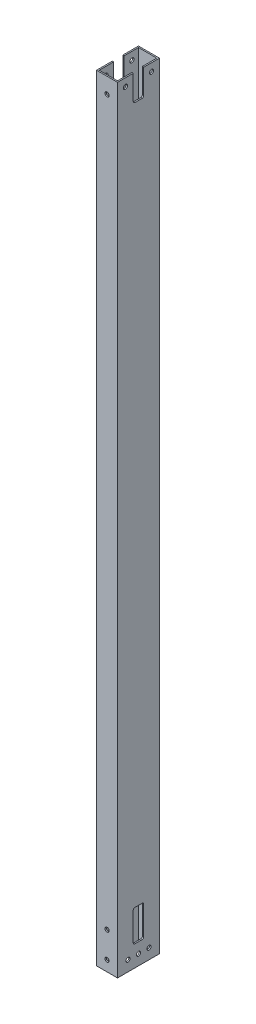
SolidWorks part; units mm, degrees
material "6061-T6 (SS)"
ref_plane "Front" through (0, 0, 0) normal (0, 0, 1) x (1, 0, 0)
ref_plane "Top" through (0, 0, 0) normal (0, 1, 0) x (1, 0, 0)
ref_plane "Right" through (0, 0, 0) normal (1, 0, 0) x (0, 0, -1)
sketch "Sketch1" plane through (0, 0, 0) normal (0, 1, 0) x (1, 0, 0)
  line L1 (12.7, 25.4) -> (-12.7, 25.4)
  line L2 (12.7, 25.4) -> (12.7, -25.4)
  line L3 (12.7, -25.4) -> (-12.7, -25.4)
  line L4 (-12.7, 25.4) -> (-12.7, -25.4)
  line L5 (12.7, 25.4) -> (-12.7, -25.4) construction
  line L6 (12.7, -25.4) -> (-12.7, 25.4) construction
  point P0 (0, 0)
  dimension "D1" = 25.4
  dimension "D2" = 50.8
extrude "Extrude-Thin1" add sketch "Sketch1" along normal blind 939.8 thin thin type one direction reverse wall 1.5875
sketch "Sketch2" plane through (-12.7, 0, 0) normal (-1, 0, 0) x (0, 0, 1)
  line L0 (-25.4, 939.8) -> (25.4, 939.8) construction
  line L1 (-6.35, 939.8) -> (6.35, 939.8)
  line L2 (-6.35, 939.8) -> (-6.35, 910.082)
  line L3 (-4.318, 908.05) -> (4.318, 908.05)
  line L4 (6.35, 939.8) -> (6.35, 910.082)
  line L5 (-25.4, 939.8) -> (-6.35, 908.05) construction
  line L6 (25.4, 939.8) -> (6.35, 908.05) construction
  line L7 (-25.4, 0) -> (25.4, 0) construction
  line L8 (-4.318, 63.5) -> (4.318, 63.5)
  line L9 (-6.35, 61.468) -> (-6.35, 27.432)
  line L10 (-4.318, 25.4) -> (4.318, 25.4)
  line L11 (6.35, 61.468) -> (6.35, 27.432)
  arc A0 (4.318, 908.05) -> (6.35, 910.082) centre (4.318, 910.082) ccw
  arc A1 (-6.35, 910.082) -> (-4.318, 908.05) centre (-4.318, 910.082) ccw
  arc A2 (-6.35, 27.432) -> (-4.318, 25.4) centre (-4.318, 27.432) ccw
  arc A3 (4.318, 25.4) -> (6.35, 27.432) centre (4.318, 27.432) ccw
  arc A4 (4.318, 63.5) -> (6.35, 61.468) centre (4.318, 61.468) cw
  arc A5 (-4.318, 63.5) -> (-6.35, 61.468) centre (-4.318, 61.468) ccw
  point P26 (6.35, 25.4)
  point P29 (6.35, 63.5)
  dimension "D3" = 2.032
  dimension "D1" = 12.7
  dimension "D2" = 31.75
  dimension "D4" = 25.4
  dimension "D5" = 38.1
extrude "Cut-Extrude1" cut sketch "Sketch2" against normal through all
sketch "Sketch5" plane through (0, 0, 25.4) normal (0, 0, 1) x (1, 0, 0)
  line L3 (-12.7, 939.8) -> (12.7, 939.8) construction
  line L4 (-12.7, 0) -> (12.7, 0) construction
  point P0 (0, 920.75)
  point P12 (0, 12.7)
  point P18 (0, 44.45)
  dimension "D1" = 19.05
  dimension "D2" = 12.7
  dimension "D3" = 44.45
hole_wizard "#10 Clearance Hole1" positions "Sketch5" profile "Sketch4" hole size "#10" standard "ANSI Inch" end condition through all
sketch "Sketch4" plane through (0, 920.75, 25.4) normal (1, 0, 0) x (0, -1, 0)
  line L0 (0, 0) -> (0, 50.8)
  line L1 (0, 50.8) -> (2.5527, 50.8)
  line L2 (2.5527, 50.8) -> (2.5527, 0)
  line L5 (2.5527, 0) -> (0, 0)
  line L11 (0, -6.35) -> (0, 107.95) construction
  dimension "Thru Hole Dia." = 5.1054
  dimension "Thru Hole Depth" = 50.8
sketch "Sketch8" plane through (-12.7, 0, 0) normal (-1, 0, 0) x (0, 0, 1)
  line L0 (-25.4, 939.8) -> (-15.875, 930.275) construction
  line L3 (25.4, 939.8) -> (15.875, 930.275) construction
  line L5 (-25.4, 939.8) -> (-6.35, 939.8) construction
  line L6 (-25.4, 939.8) -> (-25.4, 0) construction
  line L7 (-12.7, 12.7) -> (12.7, 12.7) construction
  line L9 (-25.4, 0) -> (25.4, 0) construction
  point P0 (15.875, 930.275)
  point P2 (-15.875, 930.275)
  point P20 (-12.7, 12.7)
  point P22 (0, 12.7)
  point P24 (12.7, 12.7)
  dimension "D1" = 9.525
  dimension "D2" = 9.525
  dimension "D3" = 12.7
  dimension "D4" = 12.7
hole_wizard "#10 Clearance Hole2" positions "Sketch8" profile "Sketch7" hole size "#10" standard "ANSI Inch" end condition through all
sketch "Sketch7" plane through (-12.7, 930.275, 15.875) normal (0, 1, 0) x (0, 0, 1)
  line L0 (0, 0) -> (0, 25.4)
  line L1 (0, 25.4) -> (2.5527, 25.4)
  line L2 (2.5527, 25.4) -> (2.5527, 0)
  line L5 (2.5527, 0) -> (0, 0)
  line L11 (0, -6.35) -> (0, 107.95) construction
  dimension "Thru Hole Dia." = 5.1054
  dimension "Thru Hole Depth" = 25.4
sketch "Sketch9" plane through (-12.7, 0, 0) normal (-1, 0, 0) x (0, 0, 1)
  line L0 (-25.4, 0) -> (-6.35, 25.4) construction
  line L1 (-6.35, 63.5) -> (6.35, 63.5)
  line L2 (-6.35, 63.5) -> (-6.35, 25.4)
  line L3 (-6.35, 25.4) -> (6.35, 25.4)
  line L4 (6.35, 63.5) -> (6.35, 25.4)
  line L5 (6.35, 25.4) -> (25.4, 0) construction
  line L6 (-25.4, 0) -> (25.4, 0) construction
  line L7 (25.4, 939.8) -> (25.4, 0) construction
  point P5 (0, 0)
  dimension "D1" = 12.7
  dimension "D2" = 25.4
  dimension "D3" = 38.1
extrude "Cut-Extrude2" [suppressed] cut sketch "Sketch9" against normal through all
